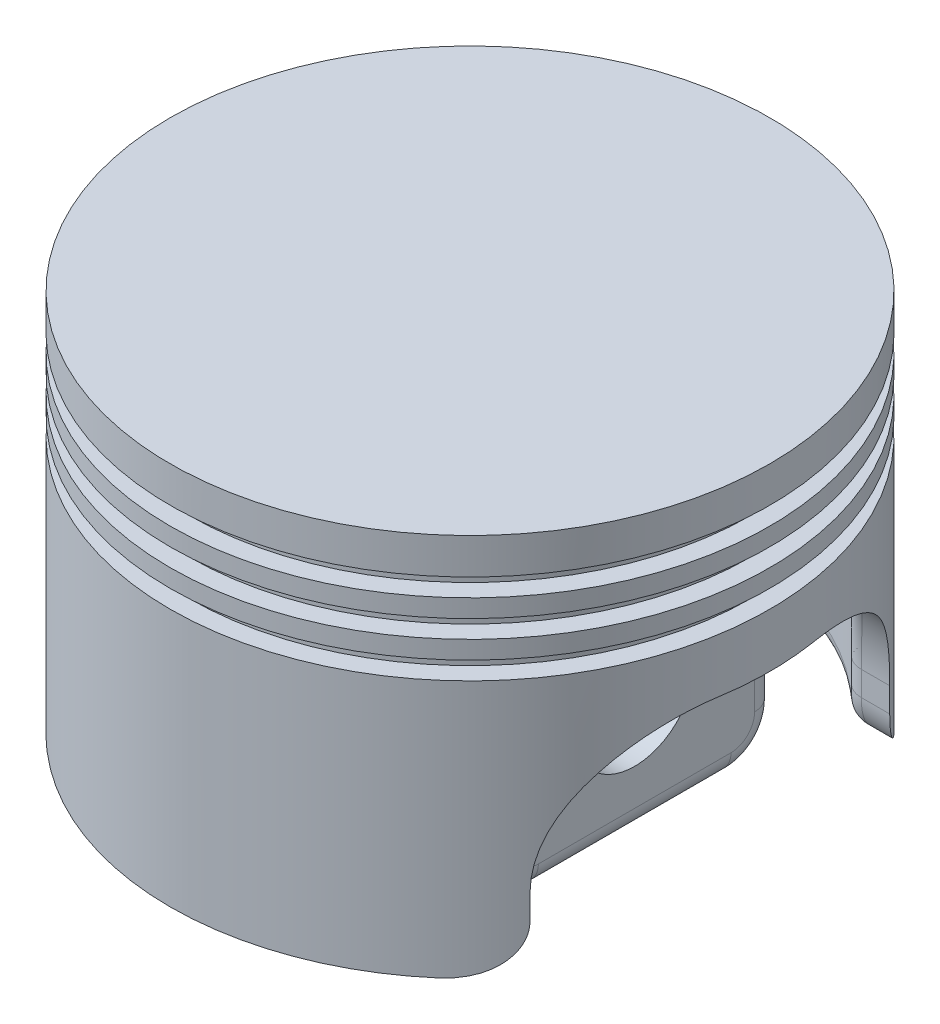
SolidWorks part; units mm, degrees
ref_plane "Front Plane" through (0, 0, 0) normal (0, 0, 1) x (1, 0, 0)
ref_plane "Top Plane" through (0, 0, 0) normal (0, 1, 0) x (1, 0, 0)
ref_plane "Right Plane" through (0, 0, 0) normal (1, 0, 0) x (0, 0, -1)
sketch "Sketch1" plane through (0, 0, 0) normal (0, 0, 1) x (1, 0, 0)
  line L0 (0, 0) -> (0, -19)
  line L1 (0, -19) -> (57.15, -19)
  line L2 (57.15, -19) -> (57.15, -81.28)
  line L3 (57.15, -81.28) -> (63.5, -81.28)
  line L4 (63.5, -81.28) -> (63.5, 0)
  line L5 (63.5, 0) -> (0, 0)
  dimension "D1" = 63.5
  dimension "D2" = 81.28
  dimension "D3" = 19
  dimension "D4" = 62.28
  dimension "57.15" = 57.15
revolve "Revolve1" add sketch "Sketch1" angle 360 about L0
sketch "Sketch2" plane through (0, 0, 0) normal (1, 0, 0) x (0, 0, -1)
  line L0 (-63.5, -81.28) -> (63.5, -81.28) construction
  line L1 (-38.1, -38.1) -> (38.1, -38.1)
  line L2 (-38.1, -38.1) -> (-38.1, -81.28)
  line L3 (-38.1, -81.28) -> (38.1, -81.28)
  line L4 (38.1, -38.1) -> (38.1, -81.28)
  line L5 (-38.1, -38.1) -> (38.1, -81.28) construction
  line L6 (-38.1, -81.28) -> (38.1, -38.1) construction
  point P0 (0, -59.69)
  point P7 (0, 0)
  point P8 (0, 0)
  dimension "D1" = 76.2
  dimension "D2" = 43.18
extrude "Cut-Extrude2" cut sketch "Sketch2" against normal through all both and the other way through all
sketch "Sketch3" plane through (0, 0, 0) normal (1, 0, 0) x (0, 0, -1)
  line L0 (0, 0) -> (0, -29.4861) construction
  line L1 (63.5, -81.28) -> (63.5, 0) construction
  line L2 (59.5332, -7.62) -> (66.6498, -7.62)
  line L3 (59.5332, -7.62) -> (59.5332, -11.43)
  line L4 (59.5332, -11.43) -> (66.6498, -11.43)
  line L5 (66.6498, -7.62) -> (66.6498, -11.43)
  line L6 (59.5332, -7.62) -> (66.6498, -11.43) construction
  line L7 (59.5332, -11.43) -> (66.6498, -7.62) construction
  line L8 (63.5, 0) -> (-63.5, 0) construction
  point P3 (63.0915, -9.525)
  point P10 (59.5332, -9.525)
  dimension "D1" = 3.81
  dimension "D2" = 3.9668
  dimension "D3" = 7.62
revolve "Cut-Revolve1" cut sketch "Sketch3" angle 360 about L0
pattern_linear "LPattern1" count 3 spacing 7.62 along (0, -1, 0) of "Cut-Revolve1"
sketch "Sketch5" plane through (0, -19, 0) normal (0, -1, 0) x (1, 0, 0)
  line L0 (0, 0) -> (0, 31.0828) construction
  line L1 (34.88, -30.4) -> (15.88, -30.4)
  line L2 (-34.88, 30.4) -> (-15.88, 30.4)
  line L3 (-34.88, 30.4) -> (-34.88, -30.4)
  line L4 (-34.88, -30.4) -> (-15.88, -30.4)
  line L5 (-15.88, 30.4) -> (-15.88, -30.4)
  line L6 (-34.88, 30.4) -> (-15.88, -30.4) construction
  line L7 (-34.88, -30.4) -> (-15.88, 30.4) construction
  line L8 (15.88, 30.4) -> (15.88, -30.4)
  line L9 (34.88, 30.4) -> (15.88, 30.4)
  line L10 (34.88, 30.4) -> (34.88, -30.4)
  point P3 (-25.38, 0)
  point P8 (0, 0)
  dimension "D1" = 19
  dimension "D2" = 60.8
  dimension "D3" = 31.76
extrude "Boss-Extrude1" add sketch "Sketch5" along normal blind 63.5
sketch "Sketch6" plane through (-34.88, 0, 0) normal (-1, 0, 0) x (0, 0, 1)
  line L0 (30.4, -82.5) -> (-30.4, -82.5) construction
  circle A0 centre (0, -57.1) radius 12.7
  point P4 (0, 0)
  dimension "D1" = 25.4
  dimension "D2" = 25.4
extrude "Cut-Extrude3" cut sketch "Sketch6" against normal through all both and the other way through all
fillet "Fillet1" radius 28 4 edges at (46.6985, -38.1, 38.1) (46.6985, -38.1, -38.1) (-46.6985, -38.1, -38.1) (-46.6985, -38.1, 38.1)
fillet "Fillet2" radius 10 8 edges at (46.6985, -81.28, -38.1) (46.6985, -81.28, 38.1) (-46.6985, -81.28, 38.1) (-46.6985, -81.28, -38.1) (-25.38, -82.5, -30.4) (-25.38, -82.5, 30.4) (25.38, -82.5, 30.4) (25.38, -82.5, -30.4)
fillet "Fillet3" radius 5 36 edges at (34.88, -45.75, -30.4) (34.88, -79.5711, -27.4711) (34.88, -45.75, 30.4) (34.88, -79.5711, 27.4711) (15.88, -45.75, 30.4) (15.88, -79.5711, 27.4711) (15.88, -45.75, -30.4) (15.88, -79.5711, -27.4711) (-15.88, -45.75, -30.4) (-15.88, -79.5711, -27.4711) (-15.88, -45.75, 30.4) (-15.88, -79.5711, 27.4711) (-34.88, -45.75, 30.4) (-34.88, -79.5711, 27.4711) (-34.88, -45.75, -30.4) (-34.88, -79.5711, -27.4711) (-40.0022, -78.1316, 40.816) (-42.5971, -68.69, 38.1) (-46.055, -51.2516, 33.8387) (-57.15, -38.1, 0) (-50.4318, -43.6881, -26.8841) (-42.5971, -68.69, -38.1) (-41.3657, -76.2692, -39.4335) (0, -81.28, -57.15) (40.0022, -78.1316, -40.816) (42.5971, -68.69, -38.1) (46.055, -51.2516, -33.8387) (57.15, -38.1, 0) (50.4318, -43.6881, 26.8841) (42.5971, -68.69, 38.1) (41.3657, -76.2692, 39.4335) (34.88, -82.5, 0) (15.88, -82.5, 0) (-15.88, -82.5, 0) (-34.88, -82.5, 0) (0, -81.28, 57.15)
fillet "Fillet4" radius 5 17 edges at (33.4155, -19, 28.9355) (25.38, -19, 30.4) (17.3445, -19, 28.9355) (15.88, -19, 0) (17.3445, -19, -28.9355) (25.38, -19, -30.4) (33.4155, -19, -28.9355) (34.88, -19, 0) (-57.15, -19, 0) (-17.3445, -19, 28.9355) (-25.38, -19, 30.4) (-33.4155, -19, 28.9355) (-34.88, -19, 0) (-33.4155, -19, -28.9355) (-25.38, -19, -30.4) (-17.3445, -19, -28.9355) (-15.88, -19, 0)
